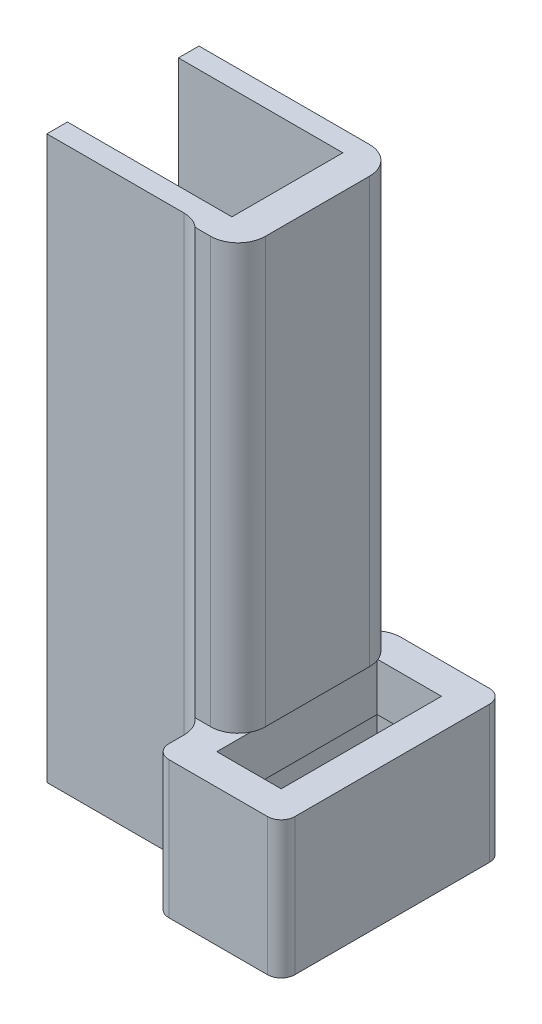
SolidWorks part; units mm, degrees
ref_plane "Alzado" through (0, 0, 0) normal (0, 0, 1) x (1, 0, 0)
ref_plane "Planta" through (0, 0, 0) normal (0, 1, 0) x (1, 0, 0)
ref_plane "Vista lateral" through (0, 0, 0) normal (1, 0, 0) x (0, 0, -1)
sketch "Croquis1" plane through (0, 0, 0) normal (0, 1, 0) x (1, 0, 0)
  line L0 (-1.5, 14.7) -> (7.7, 14.7)
  line L1 (0, 0) -> (6.2, 0)
  line L2 (0, 0) -> (0, 13.2)
  line L3 (0, 13.2) -> (6.2, 13.2)
  line L4 (6.2, 0) -> (6.2, 13.2)
  line L5 (7.7, -1.5) -> (7.7, 14.7)
  line L6 (-1.5, -1.5) -> (7.7, -1.5)
  line L7 (-1.5, -1.5) -> (-1.5, 14.7)
  dimension "D1" = 13.2
  dimension "D2" = 6.2
  dimension "D3" = 1.5
extrude "Saliente-Extruir1" add sketch "Croquis1" along normal blind 10
sketch "Croquis2" plane through (0, 10, 0) normal (0, 1, 0) x (1, 0, 0)
  line L0 (0, 13.2) -> (0, 0) construction
  line L1 (0, 0) -> (6.2, 0) construction
  line L2 (6.2, 0) -> (6.2, 13.2) construction
  line L3 (6.2, 13.2) -> (0, 13.2) construction
  line L4 (0, 13.2) -> (0, 0)
  line L5 (0, 0) -> (6.2, 0)
  line L6 (6.2, 0) -> (6.2, 13.2)
  line L7 (6.2, 13.2) -> (0, 13.2)
  line L8 (5.45, 12.45) -> (0.75, 12.45)
  line L9 (0.75, 12.45) -> (0.75, 0.75)
  line L10 (0.75, 0.75) -> (5.45, 0.75)
  line L11 (5.45, 0.75) -> (5.45, 12.45)
  dimension "D1" = 0.75
extrude "Saliente-Extruir2" add sketch "Croquis2" against normal blind 3.5
sketch "Croquis3" plane through (0, 10, 0) normal (0, 1, 0) x (1, 0, 0)
  line L0 (-1.5, 14.7) -> (-1.5, -1.5) construction
  line L1 (-9.05, 13.7) -> (0.95, 13.7)
  line L3 (-9.05, -1.3) -> (0.95, -1.3)
  line L4 (0.95, 13.7) -> (0.95, -1.3)
  line L5 (7.7, 14.7) -> (-1.5, 14.7) construction
  line L7 (-9.05, 13.7) -> (-9.05, 12.2)
  line L8 (5.45, 0.75) -> (5.45, 12.45) construction
  line L9 (-9.05, 4.1) -> (-9.05, -1.3)
  line L10 (-9.05, 12.2) -> (-1.5, 12.2)
  line L12 (-9.05, 4.1) -> (-1.5, 4.1)
  line L13 (-1.5, 12.2) -> (-1.5, 4.1)
  dimension "D1" = 10
  dimension "D2" = 15
  dimension "D3" = 1
  dimension "D4" = 4.5
  dimension "D5" = 8.1
  dimension "D6" = 1.5
extrude "Saliente-Extruir3" add sketch "Croquis3" along normal blind 31
sketch "Croquis5" plane through (0, 10, 0) normal (0, -1, 0) x (1, 0, 0)
  line L4 (-9.05, -13.7) -> (-1.5, -13.7)
  line L5 (-1.5, -13.7) -> (-1.5, -12.2)
  line L6 (-1.5, -12.2) -> (-9.05, -12.2)
  line L7 (-9.05, -12.2) -> (-9.05, -13.7)
  line L8 (-9.05, -13.7) -> (-1.5, -13.7)
  line L9 (-1.5, -13.7) -> (-1.5, -12.2)
  line L10 (-1.5, -12.2) -> (-9.05, -12.2)
  line L11 (-9.05, -12.2) -> (-9.05, -13.7)
  line L12 (-9.05, -4.1) -> (-1.5, -4.1)
  line L13 (-1.5, -4.1) -> (-1.5, 1.3)
  line L14 (-1.5, 1.3) -> (-9.05, 1.3)
  line L15 (-9.05, 1.3) -> (-9.05, -4.1)
  line L16 (-9.05, -4.1) -> (-1.5, -4.1)
  line L17 (-1.5, -4.1) -> (-1.5, 1.3)
  line L18 (-1.5, 1.3) -> (-9.05, 1.3)
  line L19 (-9.05, 1.3) -> (-9.05, -4.1)
  dimension "D1" = 0
  dimension "D2" = 0
extrude "Saliente-Extruir5" add sketch "Croquis5" along normal up to surface (10 mm away) up to face at (3.1, 0, -6.6)
fillet "Redondeo2" radius 2 1 edges at (-1.5, 5, -14.7)
sketch "Croquis6" plane through (0, 0, 0) normal (0, -1, 0) x (1, 0, 0)
  line L0 (-1.5, -12.2) -> (-1.5, -4.1) construction
  line L1 (-9.05, 1.3) -> (-1.5, 1.3)
  line L2 (-9.05, 1.3) -> (-9.05, -2.6)
  line L3 (-9.05, -2.6) -> (-1.5, -2.6)
  line L4 (-1.5, 1.3) -> (-1.5, -2.6)
  line L5 (-9.05, -4.1) -> (-1.5, -4.1) construction
  dimension "D1" = 1.5
extrude "Cortar-Extruir1" cut sketch "Croquis6" against normal up to surface (41 mm away) up to face at (-4.6625, 41, -7.175)
sketch "Croquis7" plane through (0, 41, 0) normal (0, 1, 0) x (1, 0, 0)
  line L0 (0.95, -1.3) -> (0.95, 13.7) construction
  line L1 (-1.5, -1.3) -> (0.95, -1.3)
  line L2 (-1.5, -1.3) -> (-1.5, 2.1)
  line L3 (-1.5, 2.1) -> (0.95, 2.1)
  line L4 (0.95, -1.3) -> (0.95, 2.1)
  dimension "D1" = 3.4
extrude "Cortar-Extruir2" cut sketch "Croquis7" against normal up to surface (31 mm away) up to face at (2.1415, 10, -6.486)
fillet "Redondeo3" radius 2 3 edges at (-1.5, 20.5, -2.6) (0.95, 25.5, -13.7) (0.95, 25.5, -2.1)
fillet "Redondeo4" radius 1 3 edges at (7.7, 5, -14.7) (7.7, 5, 1.5) (-1.5, 5, 1.5)
sketch "Croquis8" plane through (-9.05, 0, 0) normal (-1, 0, 0) x (0, 0, 1)
  line L4 (-4.1, 0) -> (-2.6, 0)
  line L5 (-2.6, 0) -> (-2.6, 41)
  line L6 (-2.6, 41) -> (-4.1, 41)
  line L7 (-4.1, 41) -> (-4.1, 0)
  line L8 (-4.1, 0) -> (-2.6, 0)
  line L9 (-2.6, 0) -> (-2.6, 41)
  line L10 (-2.6, 41) -> (-4.1, 41)
  line L11 (-4.1, 41) -> (-4.1, 0)
  line L12 (-13.7, 41) -> (-13.7, 0)
  line L13 (-13.7, 0) -> (-12.2, 0)
  line L14 (-12.2, 0) -> (-12.2, 41)
  line L15 (-12.2, 41) -> (-13.7, 41)
  line L16 (-13.7, 41) -> (-13.7, 0)
  line L17 (-13.7, 0) -> (-12.2, 0)
  line L18 (-12.2, 0) -> (-12.2, 41)
  line L19 (-12.2, 41) -> (-13.7, 41)
  dimension "D1" = 0
  dimension "D2" = 0
extrude "Saliente-Extruir6" add sketch "Croquis8" along normal blind 4.45
